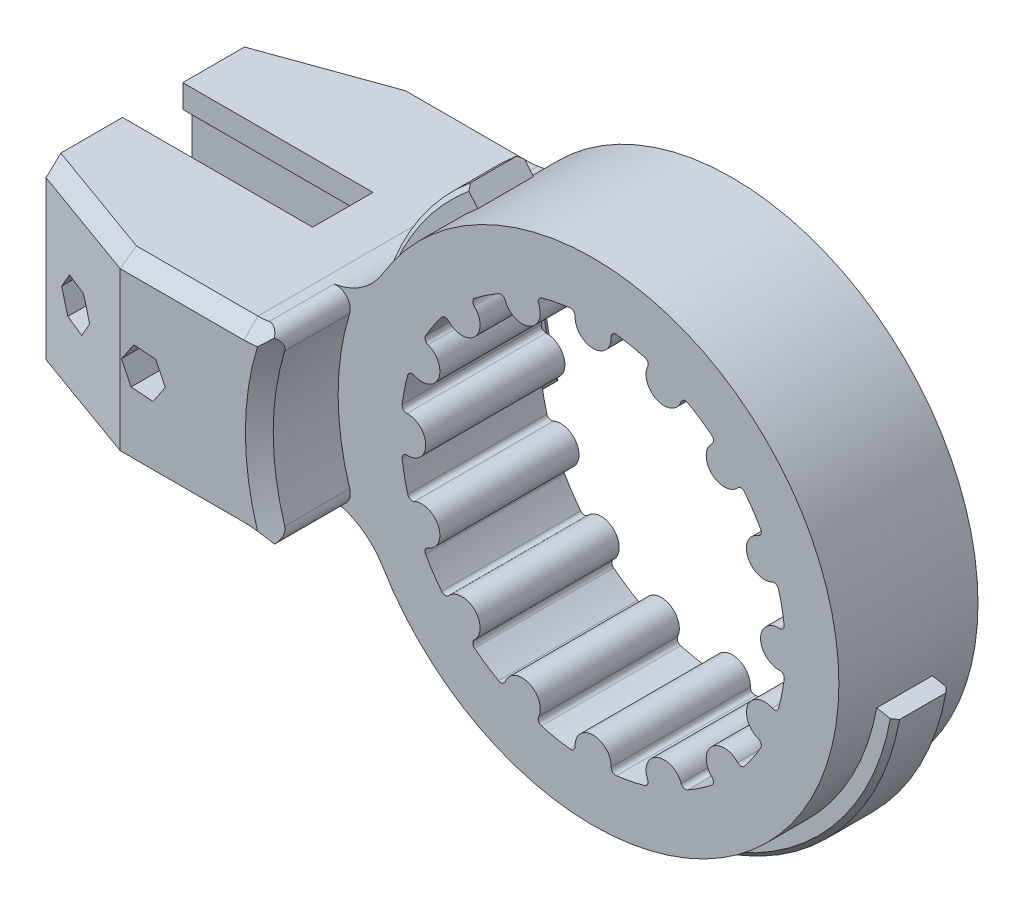
SolidWorks part; units mm, degrees
ref_plane "Front Plane" through (0, 0, 0) normal (0, 0, 1) x (1, 0, 0)
ref_plane "Top Plane" through (0, 0, 0) normal (0, 1, 0) x (1, 0, 0)
ref_plane "Right Plane" through (0, 0, 0) normal (1, 0, 0) x (0, 0, -1)
sketch "Sketch1" plane through (0, 0, 0) normal (0, 0, 1) x (1, 0, 0)
  circle A0 centre (0, 0) radius 53
  dimension "D1" = 106
extrude "Boss-Extrude1" add sketch "Sketch1" along normal blind 30
sketch "Sketch4" plane through (0, 0, 0) normal (0, 0, -1) x (-1, 0, 0)
  line L0 (53, 0) -> (110, 0) construction
  line L1 (49.0816, -20) -> (110, -20)
  line L2 (49.0816, 20) -> (110, 20)
  line L3 (110, 20) -> (110, -20)
  line L4 (0, 20) -> (110, 20) construction
  line L5 (0, 0) -> (110, 0) construction
  line L6 (0, -20) -> (110, -20) construction
  circle A0 centre (0, 0) radius 53 construction
  arc A1 (49.0816, -20) -> (49.0816, 20) centre (0, 0) ccw
  dimension "D3" = 110
  dimension "D1" = 20
  dimension "D2" = 20
extrude "Boss-Extrude2" add sketch "Sketch4" against normal up to surface (30 mm away) up to face at (53, 0, 30)
sketch "Sketch5" plane through (0, 0, 0) normal (0, 0, -1) x (-1, 0, 0)
  line L2 (110, -20) -> (110, 20)
  line L3 (110, 20) -> (51.2348, 20)
  line L5 (51.2348, -20) -> (110, -20)
  line L6 (0, 0) -> (139.0391, 0) construction
  arc A0 (51.2348, -20) -> (51.2348, 20) centre (0, 0) ccw
  dimension "D1" = 110
  dimension "D2" = 40
  dimension "D3" = 110
extrude "Boss-Extrude3" add sketch "Sketch5" along normal blind 17
sketch "Sketch6" plane through (0, 0, 30) normal (0, 0, 1) x (1, 0, 0)
  line L0 (-110, 0) -> (0, 0) construction
  line L6 (-110, -20) -> (-51.2348, -20)
  line L7 (-110, 20) -> (-110, -20)
  line L8 (-51.2348, 20) -> (-110, 20)
  arc A2 (-51.2348, 20) -> (-51.2348, -20) centre (0, 0) ccw
  dimension "D1" = 55
  dimension "D2" = 40
  dimension "D3" = 110
extrude "Boss-Extrude4" add sketch "Sketch6" along normal blind 17
sketch "Sketch7" plane through (0, 20, 0) normal (0, 1, 0) x (1, 0, 0)
  line L0 (53, -15) -> (-110, -15) construction
  line L1 (53, -30) -> (53, 0) construction
  line L2 (-110, -47) -> (-110, 17) construction
  line L4 (-151, -8.5) -> (-69, -8.5)
  line L5 (-151, -8.5) -> (-151, -21.5)
  line L6 (-151, -21.5) -> (-69, -21.5)
  line L7 (-69, -8.5) -> (-69, -21.5)
  line L8 (-151, -8.5) -> (-69, -21.5) construction
  line L9 (-151, -21.5) -> (-69, -8.5) construction
  dimension "D1" = 13
  dimension "D2" = 41
extrude "Cut-Extrude3" cut sketch "Sketch7" against normal through all
sketch "Sketch8" plane through (0, 20, 0) normal (0, 1, 0) x (1, 0, 0)
  line L0 (-110, 8) -> (-85, 17)
  line L1 (-110, -8.5) -> (-110, 17) construction
  line L2 (-110, 17) -> (-51.2348, 17) construction
  line L3 (-69, -15) -> (-102.4865, -15) construction
  line L4 (-69, -21.5) -> (-69, -8.5) construction
  line L5 (-110, -38) -> (-85, -47)
  line L6 (-110, -47) -> (-110, -21.5) construction
  line L7 (-51.2348, -47) -> (-110, -47) construction
  line L8 (-110, 17) -> (-85, 17)
  line L9 (-110, 8) -> (-110, 17)
  line L10 (-110, -47) -> (-110, -38)
  line L11 (-85, -47) -> (-110, -47)
  dimension "D1" = 9
  dimension "D2" = 25
extrude "Cut-Extrude4" cut sketch "Sketch8" against normal through all
fillet "Fillet3" radius 15 2 edges at (-49.0816, 20, 15) (-49.0816, -20, 15)
sketch "Sketch10" plane through (-110, 0, 0) normal (-1, 0, 0) x (0, 0, 1)
  line L0 (15, 20) -> (15, -20) construction
  line L1 (47, 20) -> (-17, 20) construction
  line L2 (-17, -20) -> (47, -20) construction
  line L3 (21.5, -20) -> (21.5, 20) construction
  line L4 (6.5, 15) -> (23.5, 15)
  line L5 (6.5, 15) -> (6.5, -15)
  line L6 (6.5, -15) -> (23.5, -15)
  line L7 (23.5, 15) -> (23.5, -15)
  line L8 (6.5, 15) -> (23.5, -15) construction
  line L9 (6.5, -15) -> (23.5, 15) construction
  point P6 (15, 0)
  dimension "D1" = 30
  dimension "D2" = 2
extrude "Cut-Extrude5" cut sketch "Sketch10" against normal blind 41
sketch "Sketch11" plane through (0, 0, -17) normal (0, 0, -1) x (-1, 0, 0)
  line L0 (110, 0) -> (45.4033, 0) construction
  line L1 (110, -20) -> (110, 20) construction
  circle A0 centre (100, 0) radius 2.75
  circle A1 centre (80, 0) radius 2.75
  dimension "D3" = 5.5
  dimension "D1" = 10
  dimension "D2" = 20
extrude "Cut-Extrude6" cut sketch "Sketch11" against normal through all
sketch "Sketch12" plane through (0, 0, -17) normal (0, 0, -1) x (-1, 0, 0)
  circle A0 centre (80, 0) radius 4.6
  circle A1 centre (100, 0) radius 4.6
  dimension "D1" = 9.2
extrude "Cut-Extrude7" cut sketch "Sketch12" against normal blind 12
sketch "Sketch13" plane through (0, 0, 47) normal (0, 0, 1) x (1, 0, 0)
  line L1 (-104.7224, 0.3346) -> (-102.651, -3.9225)
  line L2 (-102.651, -3.9225) -> (-97.9285, -4.257)
  line L3 (-97.9285, -4.257) -> (-95.2776, -0.3346)
  line L4 (-95.2776, -0.3346) -> (-97.349, 3.9225)
  line L5 (-97.349, 3.9225) -> (-102.0715, 4.257)
  line L6 (-102.0715, 4.257) -> (-104.7224, 0.3346)
  line L7 (-84.7224, 0.3346) -> (-82.651, -3.9225)
  line L8 (-82.651, -3.9225) -> (-77.9285, -4.257)
  line L9 (-77.9285, -4.257) -> (-75.2776, -0.3346)
  line L10 (-75.2776, -0.3346) -> (-77.349, 3.9225)
  line L11 (-77.349, 3.9225) -> (-82.0715, 4.257)
  line L12 (-82.0715, 4.257) -> (-84.7224, 0.3346)
  circle A0 centre (-100, 0) radius 4.1 construction
  circle A1 centre (-80, 0) radius 4.1 construction
  dimension "D1" = 8.2
extrude "Cut-Extrude8" cut sketch "Sketch13" against normal blind 12
sketch3d "3DSketch1"
  line L0 (-58.3009, 20, 47) -> (-85, 20, 47) construction
  line L1 (-85, -20, 47) -> (-85, 20, 47) construction
  point P0 (-54.8705, 20, 47)
  point P1 (-85, 11.3679, 47)
  point P4 (-110, 20, 38)
chamfer "Chamfer1" distance 3 angle 45 7 edges at (-97.5, 20, 42.5) (-71.6505, 20, 47) (-55, 0, 47) (-97.5, -20, 42.5) (-71.6505, -20, 47) (-54.1139, -20.5962, 47) (-54.1139, 20.5962, 47)
chamfer "Chamfer2" distance 3 angle 45 7 edges at (-97.5, -20, -12.5) (-71.6505, -20, -17) (-55, 0, -17) (-71.6505, 20, -17) (-97.5, 20, -12.5) (-54.1139, 20.5962, -17) (-54.1139, -20.5962, -17)
ref_plane "Plane2" through (0, 0, 15) normal (0, 0, 1) x (1, 0, 0)
fillet "Fillet5" radius 3 4 edges at (-50.2597, -22.3375, -7) (-50.2597, -22.3375, 37) (-50.2597, 22.3375, -7) (-50.2597, 22.3375, 37)
sketch "Sketch25" plane through (0, 0, 15) normal (0, 0, 1) x (1, 0, 0)
  circle A0 centre (0, 0) radius 57
  circle A1 centre (0, 0) radius 53
  arc A2 (-45.4404, -27.2794) -> (-45.4404, 27.2794) centre (0, 0) ccw construction
  dimension "D1" = 4
extrude "Boss-Extrude8" add sketch "Sketch25" along normal mid plane 12
sketch "Sketch26" plane through (0, 0, 21) normal (0, 0, 1) x (1, 0, 0)
  line L0 (56.0861, -10.1662) -> (52.1502, -9.4528)
  line L2 (-36.4297, 43.8392) -> (-33.8733, 40.7627)
  arc A0 (-53.0039, -20.9664) -> (-53.0039, 20.9664) centre (0, 0) ccw construction
  arc A1 (-45.4404, -27.2794) -> (-45.4404, 27.2794) centre (0, 0) ccw construction
  arc A2 (56.0861, -10.1662) -> (-36.4297, 43.8392) centre (0, 0) ccw
  arc A3 (52.1502, -9.4528) -> (-33.8733, 40.7627) centre (0, 0) ccw
  dimension "D1" = 140
extrude "Cut-Extrude12" cut sketch "Sketch26" against normal blind 15
chamfer "Chamfer4" distance 1 angle 45 4 edges at (5.6157, -56.7227, 21) (5.6157, -56.7227, 9) (-46.1561, 33.4457, 9) (-46.1561, 33.4457, 21)
sketch "Sketch27" plane through (0, 0, 30) normal (0, 0, 1) x (1, 0, 0)
  circle A0 centre (0, 0) radius 40 construction
  arc A1 (-41.338, -3.6633) -> (-41.338, 3.6633) centre (-40, 0) ccw
  arc A2 (-39.5932, 12.4349) -> (-36.7894, 19.2038) centre (-36.9552, 15.3073) ccw
  arc A3 (-31.8207, 26.64) -> (-26.64, 31.8207) centre (-28.2843, 28.2843) ccw
  arc A4 (-19.2038, 36.7894) -> (-12.4349, 39.5932) centre (-15.3073, 36.9552) ccw
  arc A5 (-3.6633, 41.338) -> (3.6633, 41.338) centre (0, 40) ccw
  arc A6 (12.4349, 39.5932) -> (19.2038, 36.7894) centre (15.3073, 36.9552) ccw
  arc A7 (26.64, 31.8207) -> (31.8207, 26.64) centre (28.2843, 28.2843) ccw
  arc A8 (36.7894, 19.2038) -> (39.5932, 12.4349) centre (36.9552, 15.3073) ccw
  arc A9 (41.338, 3.6633) -> (41.338, -3.6633) centre (40, 0) ccw
  arc A10 (39.5932, -12.4349) -> (36.7894, -19.2038) centre (36.9552, -15.3073) ccw
  arc A11 (31.8207, -26.64) -> (26.64, -31.8207) centre (28.2843, -28.2843) ccw
  arc A12 (19.2038, -36.7894) -> (12.4349, -39.5932) centre (15.3073, -36.9552) ccw
  arc A13 (3.6633, -41.338) -> (-3.6633, -41.338) centre (0, -40) ccw
  arc A14 (-12.4349, -39.5932) -> (-19.2038, -36.7894) centre (-15.3073, -36.9552) ccw
  arc A15 (-26.64, -31.8207) -> (-31.8207, -26.64) centre (-28.2843, -28.2843) ccw
  arc A16 (-36.7894, -19.2038) -> (-39.5932, -12.4349) centre (-36.9552, -15.3073) ccw
  arc A17 (-12.4349, -39.5932) -> (-3.6633, -41.338) centre (0, 0) ccw
  arc A18 (3.6633, -41.338) -> (12.4349, -39.5932) centre (0, 0) ccw
  arc A19 (19.2038, -36.7894) -> (26.64, -31.8207) centre (0, 0) ccw
  arc A20 (31.8207, -26.64) -> (36.7894, -19.2038) centre (0, 0) ccw
  arc A21 (39.5932, -12.4349) -> (41.338, -3.6633) centre (0, 0) ccw
  arc A22 (41.338, 3.6633) -> (39.5932, 12.4349) centre (0, 0) ccw
  arc A23 (36.7894, 19.2038) -> (31.8207, 26.64) centre (0, 0) ccw
  arc A24 (26.64, 31.8207) -> (19.2038, 36.7894) centre (0, 0) ccw
  arc A25 (12.4349, 39.5932) -> (3.6633, 41.338) centre (0, 0) ccw
  arc A26 (-3.6633, 41.338) -> (-12.4349, 39.5932) centre (0, 0) ccw
  arc A27 (-19.2038, 36.7894) -> (-26.64, 31.8207) centre (0, 0) ccw
  arc A28 (-31.8207, 26.64) -> (-36.7894, 19.2038) centre (0, 0) ccw
  arc A29 (-39.5932, 12.4349) -> (-41.338, 3.6633) centre (0, 0) ccw
  arc A30 (-41.338, -3.6633) -> (-39.5932, -12.4349) centre (0, 0) ccw
  arc A31 (-36.7894, -19.2038) -> (-31.8207, -26.64) centre (0, 0) ccw
  arc A32 (-26.64, -31.8207) -> (-19.2038, -36.7894) centre (0, 0) ccw
  point P38 (0, 0)
  dimension "D1" = 80
  dimension "D2" = 7.8
  dimension "D4" = 1.5
  dimension "D3" = 16
extrude "Cut-Extrude13" cut sketch "Sketch27" against normal through all
fillet "Fillet6" radius 1 32 edges at (19.2038, -36.7894, 15) (26.64, -31.8207, 15) (31.8207, -26.64, 15) (36.7894, -19.2038, 15) (39.5932, -12.4349, 15) (41.338, -3.6633, 15) (41.338, 3.6633, 15) (39.5932, 12.4349, 15) (31.8207, 26.64, 15) (19.2038, 36.7894, 15) (3.6633, 41.338, 15) (-12.4349, 39.5932, 15) (36.7894, 19.2038, 15) (26.64, 31.8207, 15) (12.4349, 39.5932, 15) (-3.6633, 41.338, 15) (-19.2038, 36.7894, 15) (-31.8207, 26.64, 15) (-26.64, 31.8207, 15) (-36.7894, 19.2038, 15) (-39.5932, 12.4349, 15) (-41.338, 3.6633, 15) (-41.338, -3.6633, 15) (-36.7894, -19.2038, 15) (-39.5932, -12.4349, 15) (-31.8207, -26.64, 15) (-26.64, -31.8207, 15) (3.6633, -41.338, 15) (12.4349, -39.5932, 15) (-12.4349, -39.5932, 15) (-19.2038, -36.7894, 15) (-3.6633, -41.338, 15)
